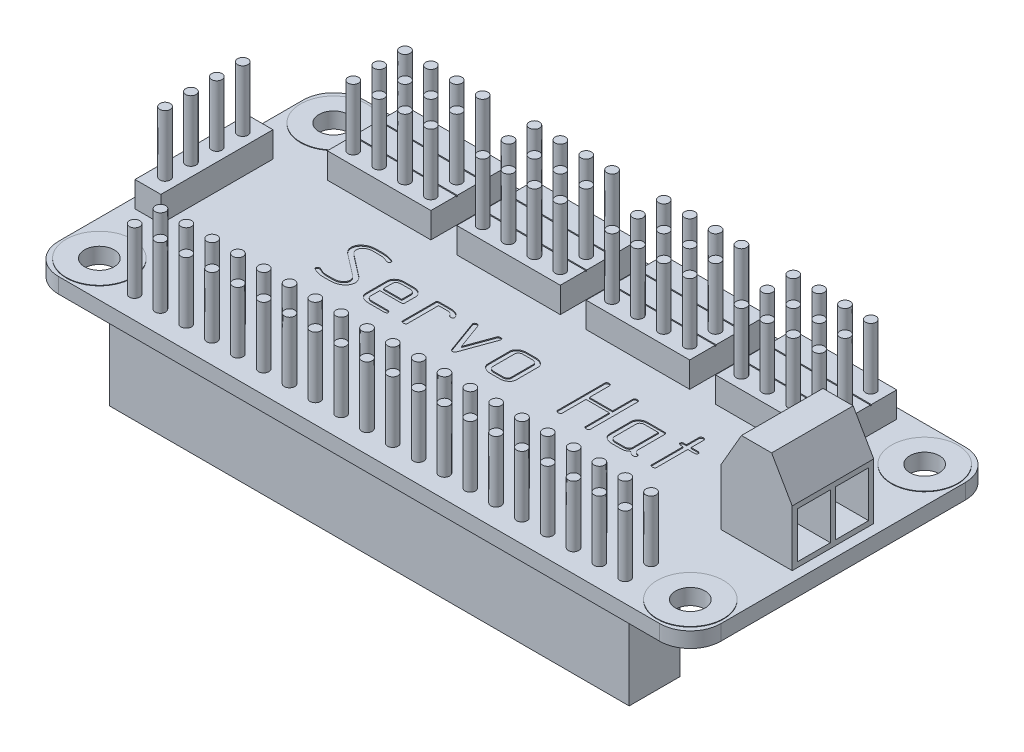
SolidWorks part; units mm, degrees
ref_plane "Спереди" through (0, 0, 0) normal (0, 0, 1) x (1, 0, 0)
ref_plane "Сверху" through (0, 0, 0) normal (0, 1, 0) x (1, 0, 0)
ref_plane "Справа" through (0, 0, 0) normal (1, 0, 0) x (0, 0, -1)
sketch "Sketch1" plane through (0, 0, 0) normal (0, 1, 0) x (1, 0, 0)
  line L1 (-32.5, 15) -> (32.5, 15)
  line L2 (-32.5, 15) -> (-32.5, -15)
  line L3 (-32.5, -15) -> (32.5, -15)
  line L4 (32.5, 15) -> (32.5, -15)
  line L5 (-32.5, 15) -> (32.5, -15) construction
  line L6 (-32.5, -15) -> (32.5, 15) construction
  point P0 (0, 0)
  dimension "D1" = 65
  dimension "D2" = 30
extrude "Основа" add sketch "Sketch1" along normal blind 1.5
sketch "Sketch2" plane through (0, 1.5, 0) normal (0, 1, 0) x (1, 0, 0)
  line L1 (29, 11.5) -> (-29, 11.5) construction
  line L2 (29, 11.5) -> (29, -11.5) construction
  line L3 (29, -11.5) -> (-29, -11.5) construction
  line L4 (-29, 11.5) -> (-29, -11.5) construction
  line L5 (29, 11.5) -> (-29, -11.5) construction
  line L6 (29, -11.5) -> (-29, 11.5) construction
  circle A0 centre (-29, 11.5) radius 1.45
  circle A1 centre (29, 11.5) radius 1.45
  circle A2 centre (29, -11.5) radius 1.45
  circle A3 centre (-29, -11.5) radius 1.45
  point P0 (0, 0)
  dimension "D3" = 2.9
  dimension "D1" = 58
  dimension "D2" = 23
extrude "Отверстия под крепеж" cut sketch "Sketch2" against normal through all
fillet "Fillet1" radius 3 4 edges at (32.5, 0.75, 15) (32.5, 0.75, -15) (-32.5, 0.75, 15) (-32.5, 0.75, -15)
sketch "Sketch3" plane through (0, 0, 0) normal (0, -1, 0) x (1, 0, 0)
  line L0 (-32.5, -12) -> (-32.5, 12) construction
  line L1 (-25.5, 14) -> (25.5, 14)
  line L2 (-25.5, 14) -> (-25.5, 9)
  line L3 (-25.5, 9) -> (25.5, 9)
  line L4 (25.5, 14) -> (25.5, 9)
  line L5 (32.5, 12) -> (32.5, -12) construction
  line L6 (-29.5, 15) -> (29.5, 15) construction
  dimension "D1" = 7
  dimension "D2" = 7
  dimension "D3" = 1
  dimension "D4" = 5
extrude "Подключение к ZERO" add sketch "Sketch3" along normal blind 8
sketch "Sketch4" plane through (0, 1.5, 0) normal (0, 1, 0) x (1, 0, 0)
  line L0 (-32.5, 12) -> (-32.5, -12) construction
  line L1 (-25.5, -9) -> (25.5, -9) construction
  line L2 (-25.5, -9) -> (-25.5, -14) construction
  line L3 (-25.5, -14) -> (25.5, -14) construction
  line L4 (25.5, -9) -> (25.5, -14) construction
  line L5 (32.5, -12) -> (32.5, 12) construction
  line L6 (-29.5, -15) -> (29.5, -15) construction
  line L7 (-25.5, -12.77) -> (-25.5, -10.23)
  line L8 (-25.5, -10.23) -> (25.5, -10.23) construction
  line L9 (-25.5, -12.77) -> (25.5, -12.77) construction
  line L10 (-24.27, -12.77) -> (-24.27, -10.23) construction
  circle A0 centre (-24.27, -10.23) radius 0.51
  circle A1 centre (-24.27, -12.77) radius 0.51
  circle A2 centre (-21.7359, -12.77) radius 0.51
  circle A3 centre (-21.7359, -10.23) radius 0.51
  circle A4 centre (-19.2019, -12.77) radius 0.51
  circle A5 centre (-19.2019, -10.23) radius 0.51
  circle A6 centre (-16.6678, -12.77) radius 0.51
  circle A7 centre (-16.6678, -10.23) radius 0.51
  circle A8 centre (-14.1338, -12.77) radius 0.51
  circle A9 centre (-14.1338, -10.23) radius 0.51
  circle A10 centre (-11.5997, -12.77) radius 0.51
  circle A11 centre (-11.5997, -10.23) radius 0.51
  circle A12 centre (-9.0657, -12.77) radius 0.51
  circle A13 centre (-9.0657, -10.23) radius 0.51
  circle A14 centre (-6.5316, -12.77) radius 0.51
  circle A15 centre (-6.5316, -10.23) radius 0.51
  circle A16 centre (-3.9976, -12.77) radius 0.51
  circle A17 centre (-3.9976, -10.23) radius 0.51
  circle A18 centre (-1.4635, -12.77) radius 0.51
  circle A19 centre (-1.4635, -10.23) radius 0.51
  circle A20 centre (1.0705, -12.77) radius 0.51
  circle A21 centre (1.0705, -10.23) radius 0.51
  circle A22 centre (3.6046, -12.77) radius 0.51
  circle A23 centre (3.6046, -10.23) radius 0.51
  circle A24 centre (6.1387, -12.77) radius 0.51
  circle A25 centre (6.1387, -10.23) radius 0.51
  circle A26 centre (8.6727, -12.77) radius 0.51
  circle A27 centre (8.6727, -10.23) radius 0.51
  circle A28 centre (11.2068, -12.77) radius 0.51
  circle A29 centre (11.2068, -10.23) radius 0.51
  circle A30 centre (13.7408, -12.77) radius 0.51
  circle A31 centre (13.7408, -10.23) radius 0.51
  circle A32 centre (16.2749, -12.77) radius 0.51
  circle A33 centre (16.2749, -10.23) radius 0.51
  circle A34 centre (18.8089, -12.77) radius 0.51
  circle A35 centre (18.8089, -10.23) radius 0.51
  circle A36 centre (21.343, -12.77) radius 0.51
  circle A37 centre (21.343, -10.23) radius 0.51
  circle A38 centre (23.877, -12.77) radius 0.51
  circle A39 centre (23.877, -10.23) radius 0.51
  point P13 (-25.5, -11.5)
  dimension "D7" = 1.02
  dimension "D1" = 7
  dimension "D2" = 7
  dimension "D3" = 1
  dimension "D4" = 5
  dimension "D5" = 2.54
  dimension "D6" = 1.23
  dimension "D8" = 20
extrude "I/O pins" add sketch "Sketch4" along normal blind 6 contours A0 | A3 | A1 | A5 | A8 | A9 | A11 | A13 | A10 | A12 | A15 | A14 | A17 | A16 | A19 | A18 | A20 | A21 | A23 | A22 | A25 | A24 | A27 | A26 | A29 | A28 | A31 | A30 | A33 | A32 | A35 | A34 | A37 | A36 | A39 | A38 | A2 | A1 | A4 | A7 | A6 region at (-24.27, 1.5, 10.23) region at (-24.27, 1.5, 12.77) region at (-21.7359, 1.5, 10.23) region at (-19.2019, 1.5, 10.23) region at (-14.1338, 1.5, 12.77) region at (-14.1338, 1.5, 10.23) region at (-11.5997, 1.5, 12.77) region at (-11.5997, 1.5, 10.23) region at (-9.0657, 1.5, 12.77) region at (-9.0657, 1.5, 10.23) region at (-6.5316, 1.5, 12.77) region at (-6.5316, 1.5, 10.23) region at (-3.9976, 1.5, 12.77) region at (-3.9976, 1.5, 10.23) region at (-1.4635, 1.5, 12.77) region at (-1.4635, 1.5, 10.23) region at (1.0705, 1.5, 12.77) region at (1.0705, 1.5, 10.23) region at (3.6046, 1.5, 12.77) region at (3.6046, 1.5, 10.23) region at (6.1387, 1.5, 12.77) region at (6.1387, 1.5, 10.23) region at (8.6727, 1.5, 12.77) region at (8.6727, 1.5, 10.23) region at (11.2068, 1.5, 12.77) region at (11.2068, 1.5, 10.23) region at (13.7408, 1.5, 12.77) region at (13.7408, 1.5, 10.23) region at (16.2749, 1.5, 12.77) region at (16.2749, 1.5, 10.23) region at (18.8089, 1.5, 12.77) region at (18.8089, 1.5, 10.23) region at (21.343, 1.5, 12.77) region at (21.343, 1.5, 10.23) region at (23.877, 1.5, 12.77) region at (23.877, 1.5, 10.23)
sketch "Sketch5" plane through (0, 1.5, 0) normal (0, 1, 0) x (1, 0, 0)
  line L0 (-29.5, -15) -> (29.5, -15) construction
  line L1 (24.5, 4) -> (31.5, 4)
  line L2 (24.5, 4) -> (24.5, -4)
  line L3 (24.5, -4) -> (31.5, -4)
  line L4 (31.5, 4) -> (31.5, -4)
  line L5 (29.5, 15) -> (-29.5, 15) construction
  line L6 (32.5, -12) -> (32.5, 12) construction
  dimension "D1" = 11
  dimension "D2" = 11
  dimension "D3" = 1
  dimension "D4" = 7
extrude "Клемник питания" add sketch "Sketch5" along normal blind 9
chamfer "Chamfer1" distance 3.5 angle 30 2 edges at (24.5, 10.5, 0) (31.5, 10.5, 0) first distance on face at (24.5, 6, 0) first distance on face at (31.5, 6, 0)
sketch "Sketch7" plane through (31.5, 0, 0) normal (1, 0, 0) x (0, 0, -1)
  line L0 (-4, 7) -> (-4, 1.5) construction
  line L1 (-3.5, 6.5) -> (-0.25, 6.5)
  line L2 (-3.5, 6.5) -> (-3.5, 2)
  line L3 (-3.5, 2) -> (-0.25, 2)
  line L4 (-0.25, 6.5) -> (-0.25, 2)
  line L5 (0.25, 6.5) -> (3.5, 6.5)
  line L6 (0.25, 6.5) -> (0.25, 2)
  line L7 (0.25, 2) -> (3.5, 2)
  line L8 (3.5, 6.5) -> (3.5, 2)
  line L9 (4, 7) -> (4, 1.5) construction
  line L10 (4, 7) -> (-4, 7) construction
  line L11 (-4, 1.5) -> (4, 1.5) construction
  line L12 (0, 7) -> (0, 1.5) construction
  dimension "D1" = 0.5
  dimension "D2" = 0.5
  dimension "D3" = 0.5
  dimension "D4" = 0.5
  dimension "D5" = 0.5
  dimension "D6" = 0.5
  dimension "D7" = 0.5
  dimension "D8" = 0.25
extrude "Extrude6" cut sketch "Sketch7" against normal blind 5
sketch "Sketch8" plane through (0, 1.5, 0) normal (0, 1, 0) x (1, 0, 0)
  line L0 (-32.5, 12) -> (-32.5, -12) construction
  line L1 (-31.5, 5.5) -> (-28.96, 5.5)
  line L2 (-31.5, 5.5) -> (-31.5, -5.5)
  line L3 (-31.5, -5.5) -> (-28.96, -5.5)
  line L4 (-28.96, 5.5) -> (-28.96, -5.5)
  line L5 (-29.5, -15) -> (29.5, -15) construction
  line L6 (29.5, 15) -> (-29.5, 15) construction
  dimension "D1" = 1
  dimension "D2" = 2.54
  dimension "D3" = 9.5
  dimension "D4" = 9.5
extrude "I2C" add sketch "Sketch8" along normal blind 2.5
sketch "Sketch9" plane through (0, 4, 0) normal (0, 1, 0) x (1, 0, 0)
  line L0 (-30.23, -5.5) -> (-30.23, 5.5) construction
  line L1 (-31.5, -5.5) -> (-28.96, -5.5) construction
  line L2 (-28.96, 5.5) -> (-31.5, 5.5) construction
  line L3 (-28.96, 5.5) -> (-31.5, 5.5) construction
  circle A0 centre (-30.23, 3.8) radius 0.51
  circle A1 centre (-30.23, 1.26) radius 0.51
  circle A2 centre (-30.23, -1.28) radius 0.51
  circle A3 centre (-30.23, -3.82) radius 0.51
  dimension "D1" = 1.02
  dimension "D2" = 1.7
  dimension "D3" = 4
extrude "Штырьки I2C" add sketch "Sketch9" along normal blind 6 and the other way blind 5
sketch "Sketch10" plane through (0, 1.5, 0) normal (0, 1, 0) x (1, 0, 0)
  line L0 (29.5, 15) -> (-29.5, 15) construction
  line L1 (-24.5, 14) -> (-14.34, 14)
  line L2 (-24.5, 14) -> (-24.5, 6.38)
  line L3 (-24.5, 6.38) -> (-14.34, 6.38)
  line L4 (-14.34, 14) -> (-14.34, 6.38)
  line L5 (-32.5, 12) -> (-32.5, -12) construction
  dimension "D1" = 7.62
  dimension "D2" = 10.16
  dimension "D3" = 1
  dimension "D4" = 8
extrude "Servo pins" add sketch "Sketch10" along normal blind 2.5
sketch "Sketch11" plane through (0, 4, 0) normal (0, 1, 0) x (1, 0, 0)
  line L0 (-23.23, 14) -> (-23.23, 6.38) construction
  line L1 (-14.34, 14) -> (-24.5, 14) construction
  line L2 (-24.5, 6.38) -> (-14.34, 6.38) construction
  line L3 (-24.5, 12.73) -> (-14.34, 12.73) construction
  line L4 (-24.5, 14) -> (-24.5, 6.38) construction
  line L5 (-14.34, 6.38) -> (-14.34, 14) construction
  line L6 (-24.5, 14) -> (-24.5, 6.38) construction
  circle A0 centre (-23.23, 12.73) radius 0.51
  dimension "D3" = 1.02
  dimension "D1" = 1.27
  dimension "D2" = 1.27
extrude "Штырьки Servo" add sketch "Sketch11" along normal blind 6 and the other way blind 5
pattern_linear "LPattern1" count 4 spacing 2.54 along (1, 0, 0) count 3 spacing 2.54 along (0, 0, 1) of "Штырьки Servo"
chamfer "Места пайки" distance 0.5 distance2 1 12 edges at (-23.23, -1, -12.22) (-20.69, -1, -12.22) (-18.15, -1, -12.22) (-15.61, -1, -12.22) (-15.61, -1, -9.68) (-18.15, -1, -9.68) (-20.69, -1, -9.68) (-23.23, -1, -9.68) (-23.23, -1, -7.14) (-20.69, -1, -7.14) (-18.15, -1, -7.14) (-15.61, -1, -7.14) first distance on face at (-23.23, -1, -12.22) first distance on face at (-20.69, -1, -12.22) first distance on face at (-18.15, -1, -12.22) first distance on face at (-15.61, -1, -12.22) first distance on face at (-15.61, -1, -9.68) first distance on face at (-18.15, -1, -9.68) first distance on face at (-20.69, -1, -9.68) first distance on face at (-23.23, -1, -9.68) first distance on face at (-23.23, -1, -7.14) first distance on face at (-20.69, -1, -7.14) first distance on face at (-18.15, -1, -7.14) first distance on face at (-15.61, -1, -7.14)
pattern_linear "LPattern2" count 4 spacing 12.7 along (1, 0, 0) of "Штырьки Servo", "LPattern1", "Места пайки", "Servo pins"
chamfer "Места пайки I2C" distance 0.5 distance2 1 4 edges at (-30.23, -1, -3.29) (-30.23, -1, 4.33) (-30.23, -1, -0.75) (-30.23, -1, 1.79) first distance on face at (-30.23, -1, -3.29) first distance on face at (-30.23, -1, 4.33) first distance on face at (-30.23, -1, -0.75) first distance on face at (-30.23, -1, 1.79)
sketch "Sketch12" plane through (0, 4, 0) normal (0, 1, 0) x (1, 0, 0)
  line L0 (-24.5, 14) -> (-24.5, 6.38) construction
  line L1 (23.76, 6.38) -> (23.76, 14) construction
  line L2 (-24.5, 8.97) -> (23.76, 8.97)
  line L3 (-24.5, 8.97) -> (-24.5, 8.87)
  line L4 (-24.5, 8.87) -> (23.76, 8.87)
  line L5 (23.76, 8.97) -> (23.76, 8.87)
  line L6 (23.76, 6.38) -> (23.76, 14) construction
  line L7 (-24.5, 11.51) -> (23.76, 11.51)
  line L8 (-24.5, 11.51) -> (-24.5, 11.41)
  line L9 (-24.5, 11.41) -> (23.76, 11.41)
  line L10 (23.76, 11.51) -> (23.76, 11.41)
  line L11 (-14.34, 14) -> (-24.5, 14) construction
  line L12 (-24.5, 6.38) -> (-14.34, 6.38) construction
  dimension "D2" = 2.49
  dimension "D3" = 2.49
extrude "Extrude11" cut sketch "Sketch12" against normal blind 0.1
sketch "Sketch13" plane through (0, 1.5, 0) normal (0, 1, 0) x (1, 0, 0)
  text T0 "Servo Hat" font "@Adobe Fan Heiti Std B" height 5
extrude "Название" cut sketch "Sketch13" against normal blind 0.1
sketch "Эскиз1" plane through (0, 0, 0) normal (0, 1, 0) x (1, 0, 0)
  circle A0 centre (-29, -11.5) radius 3.25
  circle A1 centre (-29, 11.5) radius 3.25
  circle A2 centre (29, 11.5) radius 3.25
  circle A3 centre (29, -11.5) radius 3.25
  circle A4 centre (-29, -11.5) radius 1.45 construction
  circle A5 centre (29, -11.5) radius 1.45 construction
  circle A6 centre (29, 11.5) radius 1.45 construction
  circle A7 centre (-29, 11.5) radius 1.45 construction
  circle A8 centre (-29, -11.5) radius 1.45
  circle A9 centre (29, -11.5) radius 1.45
  circle A10 centre (29, 11.5) radius 1.45
  circle A11 centre (-29, 11.5) radius 1.45
  dimension "D1" = 6.5
extrude "Бобышка-Вытянуть1" add sketch "Эскиз1" along normal offset from surface (1.55 mm away) 0.05 up to face at (-7.8226, 1.5, -0.0956) offset beyond the face yes
equation "\"D1@Sketch5\"=\"D2@Sketch5\""
equation "\"D2@Sketch7\"=\"D1@Sketch7\""
equation "\"D3@Sketch7\"=\"D1@Sketch7\""
equation "\"D4@Sketch7\"=\"D1@Sketch7\""
equation "\"D5@Sketch7\"=\"D1@Sketch7\""
equation "\"D6@Sketch7\"=\"D1@Sketch7\""
equation "\"D8@Sketch7\"=\"D7@Sketch7\"/2"
equation "\"D4@Sketch8\"=\"D3@Sketch8\""
equation "\"D2@Sketch11\"=\"D1@Sketch11\""
equation "\"D3@Sketch12\"=\"D2@Sketch12\""
